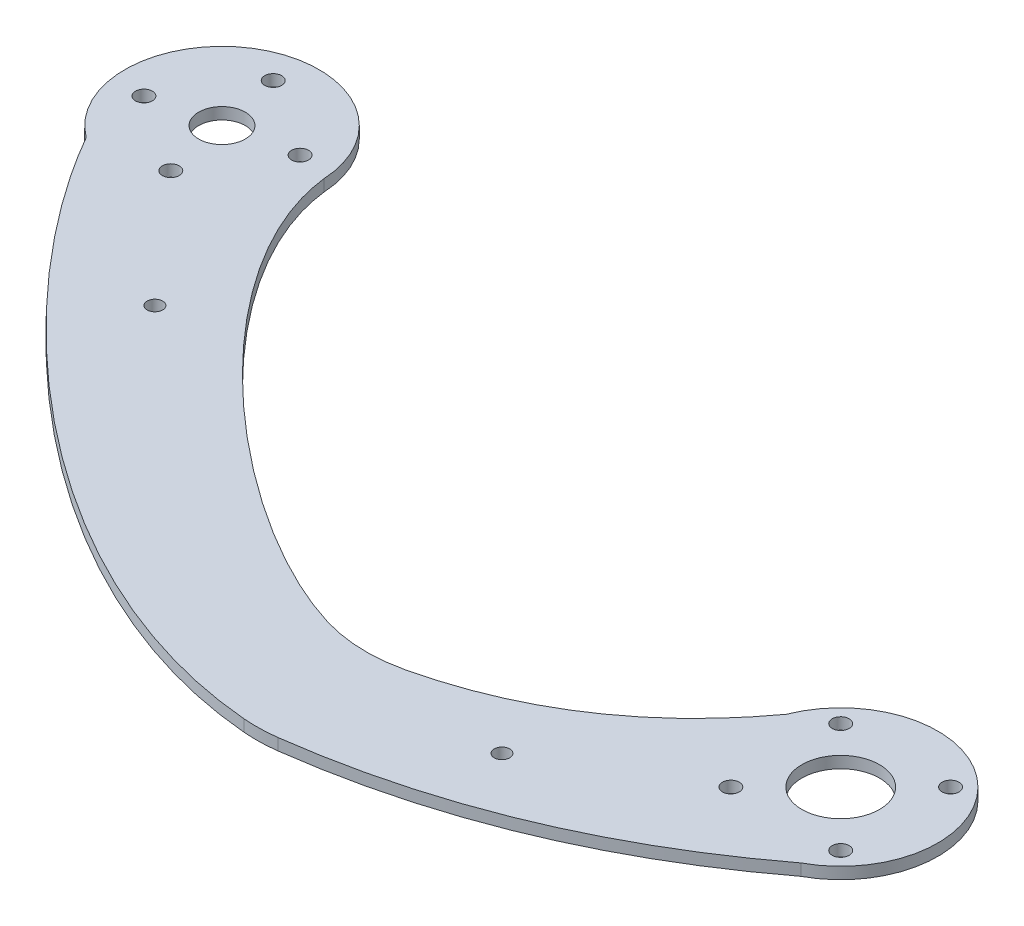
SolidWorks part; units mm, degrees
material "1060 Alloy"
ref_plane "Front" through (0, 0, 0) normal (0, 0, 1) x (1, 0, 0)
ref_plane "Top" through (0, 0, 0) normal (0, 1, 0) x (1, 0, 0)
ref_plane "Right" through (0, 0, 0) normal (1, 0, 0) x (0, 0, -1)
sketch "Sketch2" plane through (0, 0, 0) normal (0, 1, 0) x (1, 0, 0)
  point P0 (0, 0)
  line B0 (-70.9851, 36.1523) -> (-113.5823, 33.9244)
  arc B1 (5.8927, -11.0239) -> (-11.6176, 4.6132) centre (0, 0) ccw
  arc B2 (-101.0993, 34.5773) -> (-120.9882, 23.8546) centre (-113.5823, 33.9244) ccw
  spline B3 degree 3 poles (-44.5149, -15.6481) (-60.4932, -16.621) (-98.7194, 13.994) (-101.0993, 34.5773) knots 0 0 0 0 1 1 1 1
  spline B4 degree 2 poles (5.8927, -11.0239) (-16.2083, -27.8197) (-43.715, -30.9419) knots 0 0 0 1 1 1
  spline B5 degree 3 poles (-43.715, -30.9419) (-74.6559, -29.7722) (-107.9347, 0.9093) (-120.9882, 23.8546) knots 0 0 0 0 1 1 1 1
  spline B6 degree 2 poles (-44.5149, -15.6481) (-23.755, -12.0499) (-11.6176, 4.6132) knots 0 0 0 1 1 1
sketch_block_instance "Block5-1"
sketch_block "Block5" parameters "D1"=25, "D14"=79.1954, "D15"=48.0238, "D17"=92.8889, "D18"=42.1388, "D19"=62.1612, "D2"=5.3089, "D3"=16.6697, "D4"=25.1002, "D5"=50.5803, "D6"=74.3089, "D7"=104.4643, "D8"=116.9643, "D9"=124.8861, "D10"=135.8089, "D11"=34.5967, "D12"=39.8104, "D13"=51.127, "D16"=68.4269
extrude "Boss-Extrude1" add sketch "Sketch2" along normal blind 1.5 contours B5 B4 B1 B6 B3 B2 region at (-18.1336, 0, 22.9214)
fillet "Fillet2" radius 20 1 edges at (-44.5149, 0.75, 15.6481)
fillet "Fillet3" radius 20 1 edges at (-43.715, 0.75, 30.9419)
ref_plane "Plane1" through (0, 1.5, 0) normal (0, 1, 0) x (1, 0, 0)
sketch "Sketch3" plane through (0, 1.5, 0) normal (0, 1, 0) x (1, 0, 0)
  line L0 (0, 0) -> (0, 56.3072) construction
  line L1 (-7.0711, 7.0711) -> (0, 0) construction
  line L2 (-113.5823, 33.9244) -> (0, 0) construction
  line L3 (-56.7911, 16.9622) -> (-30.8992, 103.6508) construction
  line L4 (-103.7915, 35.9592) -> (-113.5823, 33.9244) construction
  line L5 (-115.6171, 43.7152) -> (-113.5823, 33.9244) construction
  line L6 (-103.7915, 35.9592) -> (-113.5823, 33.9244) construction
  line L7 (-111.5474, 24.1336) -> (-113.5823, 33.9244) construction
  line L8 (-123.3731, 31.8896) -> (-113.5823, 33.9244) construction
  circle A0 centre (0, 0) radius 5
  circle A1 centre (-7.0711, 7.0711) radius 1.09
  circle A2 centre (7.0711, 7.0711) radius 1.09
  circle A3 centre (7.0711, -7.0711) radius 1.09
  circle A4 centre (-7.0711, -7.0711) radius 1.09
  circle A5 centre (-113.5823, 33.9244) radius 3
  circle A6 centre (-105.2601, 35.654) radius 1.09
  circle A7 centre (-111.8527, 25.6023) radius 1.09
  circle A8 centre (-121.9044, 32.1948) radius 1.09
  circle A10 centre (-115.3119, 42.2466) radius 1.09
  point P8 (-56.7911, 16.9622)
  point P15 (0, 0)
  point P35 (-113.5823, 33.9244)
  dimension "D1" = 10
  dimension "D2" = 2.18
  dimension "D6" = 6
  dimension "D7" = 2.18
  dimension "D8" = 8.5
  dimension "D3" = 45
  dimension "D4" = 10
  dimension "D5" = 4
  dimension "D9" = 4
extrude "Cut-Extrude2" cut sketch "Sketch3" against normal blind 10
sketch "Sketch4" plane through (0, 1.5, 0) normal (0, 1, 0) x (1, 0, 0)
  line L0 (-113.5823, 33.9244) -> (-69.4661, -34.4033) construction
  line L1 (0, 0) -> (-63.0101, -44.4968) construction
  circle A0 centre (-97.8402, 9.543) radius 1
  circle A1 centre (-25.5617, -18.0513) radius 1
  dimension "D1" = 2
  dimension "D2" = 25.5617
  dimension "D3" = 97.8402
  dimension "D4" = 9.543
  dimension "D5" = 18.0513
extrude "Cut-Extrude3" cut sketch "Sketch4" against normal blind 10
